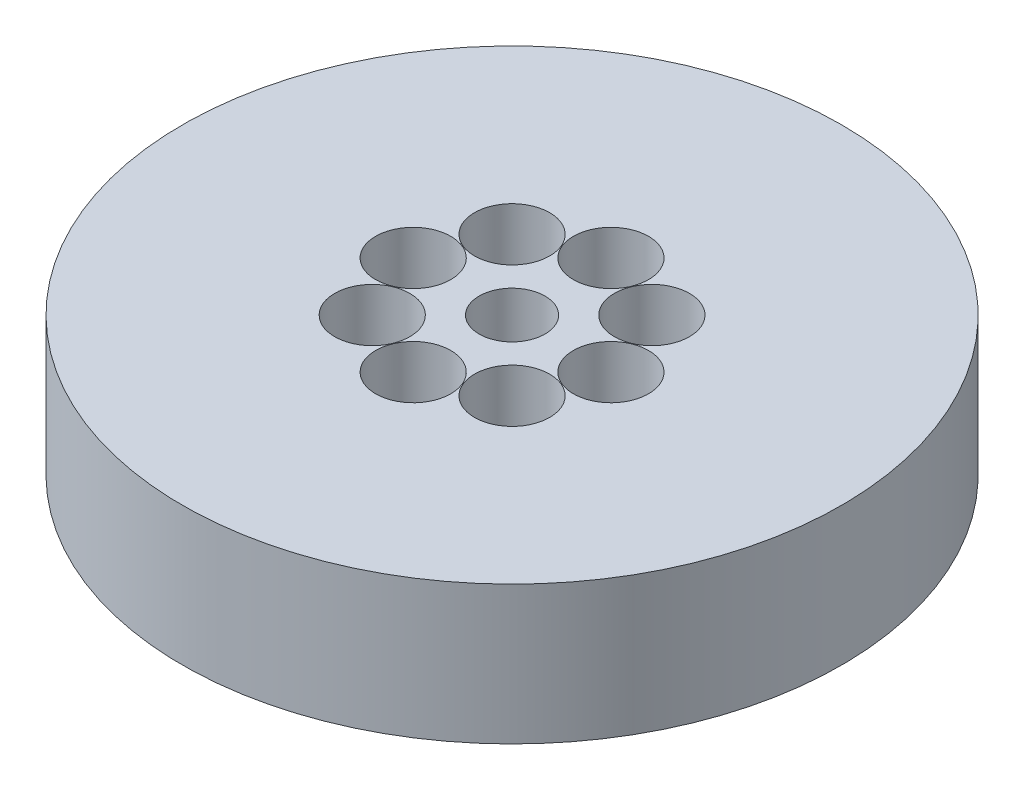
SolidWorks part; units mm, degrees
ref_plane "Front Plane" through (0, 0, 0) normal (0, 0, 1) x (1, 0, 0)
ref_plane "Top Plane" through (0, 0, 0) normal (0, 1, 0) x (1, 0, 0)
ref_plane "Right Plane" through (0, 0, 0) normal (1, 0, 0) x (0, 0, -1)
sketch "Sketch1" plane through (0, 0, 0) normal (0, 1, 0) x (1, 0, 0)
  circle A0 centre (0, 0) radius 50
  dimension "FLANGE_OD" = 100
extrude "Boss-Extrude1" add sketch "Sketch1" along normal blind 21
sketch "Sketch2" plane through (0, 0, 0) normal (0, 1, 0) x (1, 0, 0)
  circle A0 centre (0, 0) radius 5
  dimension "BORE_D" = 10
extrude "Cut-Extrude1" cut sketch "Sketch2" along normal through all
sketch "Sketch3" plane through (0, 21, 0) normal (0, 1, 0) x (1, 0, 0)
  circle A0 centre (0, 0) radius 14.9996 construction
  circle A1 centre (-14.9996, 0) radius 5.6995
  dimension "BOLT_D" = 11.3989
  dimension "BOLT_PCD" = 29.9993
extrude "Cut-Extrude2" cut sketch "Sketch3" against normal blind 20.5266
pattern_circular "CirPattern1" count 8 over 360 about axis through (0, 0, 0) along (0, 1, 0) of "Cut-Extrude2"
